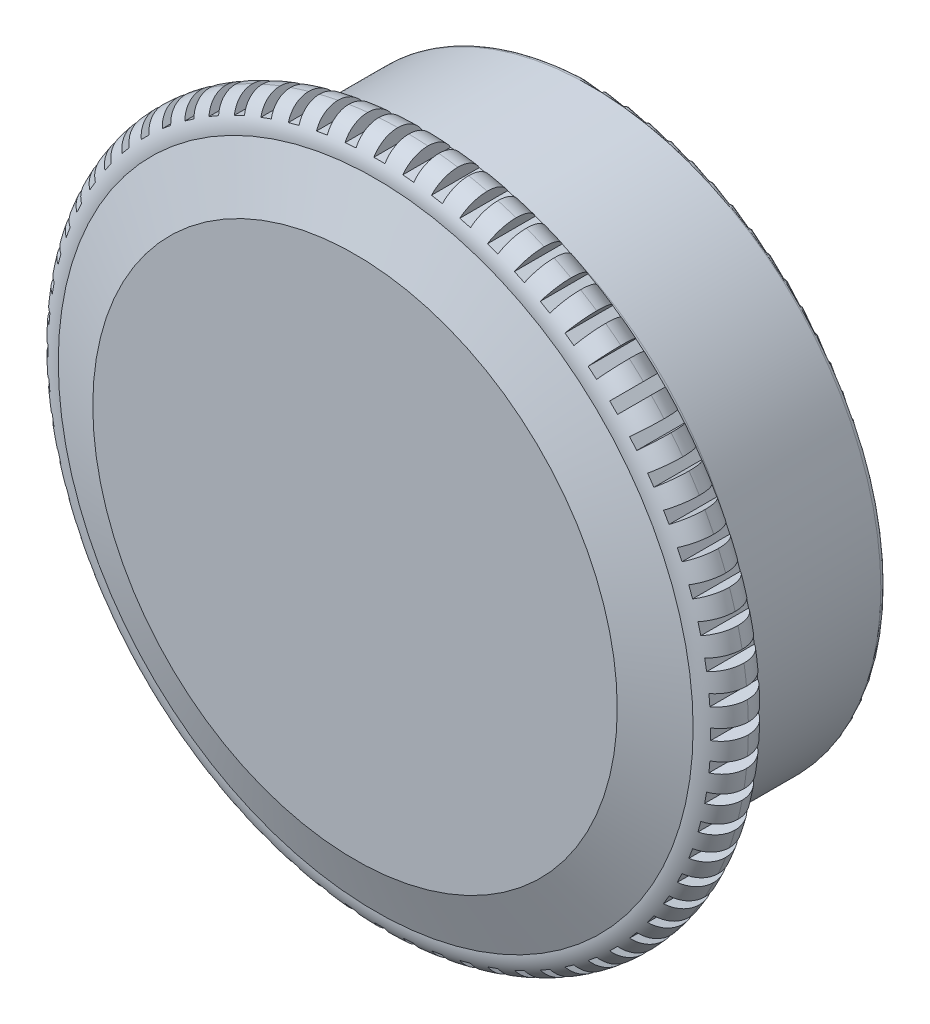
SolidWorks part; units mm, degrees
material "Mosaz"
ref_plane "Přední rovina" through (0, 0, 0) normal (0, 0, 1) x (1, 0, 0)
ref_plane "Horní rovina" through (0, 0, 0) normal (0, 1, 0) x (1, 0, 0)
ref_plane "Pravá rovina" through (0, 0, 0) normal (1, 0, 0) x (0, 0, -1)
sketch "Skica1" plane through (0, 0, 0) normal (0, 0, 1) x (1, 0, 0)
  circle A0 centre (0, 0) radius 10.5
  dimension "D1" = 21
extrude "Přidat vysunutím1" add sketch "Skica1" along normal blind 6
sketch "Skica2" plane through (0, 0, 6) normal (0, 0, 1) x (1, 0, 0)
  circle A0 centre (0, 0) radius 12.5
  dimension "D1" = 25
extrude "Přidat vysunutím2" add sketch "Skica2" along normal blind 2
fillet "Zaoblit1" radius 1 1 edges at (10.5, 0, 6)
fillet "Zaoblit2" radius 1 2 edges at (12.5, 0, 8) (12.5, 0, 6)
ref_plane "Rovina1" through (0, 12.5, 0) normal (0, 1, 0) x (1, 0, 0)
sketch "Skica4" plane through (0, 12.5, 0) normal (0, 1, 0) x (1, 0, 0)
  line L0 (12.5, -7) -> (-12.5, -7) construction
  line L2 (0, -2.5343) -> (0, -13.2979) construction
  line L3 (-0.2, -6) -> (0.2, -6)
  line L4 (-0.2, -6) -> (-0.2, -8)
  line L5 (-0.2, -8) -> (0.2, -8)
  line L6 (0.2, -6) -> (0.2, -8)
  dimension "D1" = 0.2
  dimension "D2" = 0.2
  dimension "D3" = 2
  dimension "D4" = 1
extrude "Odebrat vysunutím2" cut sketch "Skica4" against normal blind 0.5
ref_axis "Osa1" through (0, 0, 5) along (0, 0, -1)
pattern_circular "Kruhové pole1" count 72 over 360 about axis through (0, 0, 5) along (0, 0, -1) of "Odebrat vysunutím2"
sketch "Skica5" plane through (0, 0, 0) normal (0, 1, 0) x (1, 0, 0)
  line L0 (-11.5, -8) -> (-9.5, -8.7494)
  line L1 (-9.5, -8.7494) -> (0, -8.7494)
  line L2 (0, -8) -> (0, -8.7494)
  line L3 (-11.5, -8) -> (11.5, -8) construction
  line L4 (-11.5, -8) -> (0, -8)
  dimension "D1" = 9.5
  dimension "D2" = 2
revolve "Rotovat1" add sketch "Skica5" angle 360 about axis through (0, 0, 5) along (0, 0, -1)
sketch "Skica6" plane through (0, 0, 0) normal (0, 0, -1) x (-1, 0, 0)
  circle A0 centre (0, 0) radius 10
  dimension "D1" = 20
extrude "Odebrat vysunutím3" cut sketch "Skica6" against normal blind 5
cosmetic thread "Kosmetický závit1" parameters "D1"=5, "D2"=22
fillet "Zaoblit3" radius 0.2 1 edges at (10.5, 0, 0)
